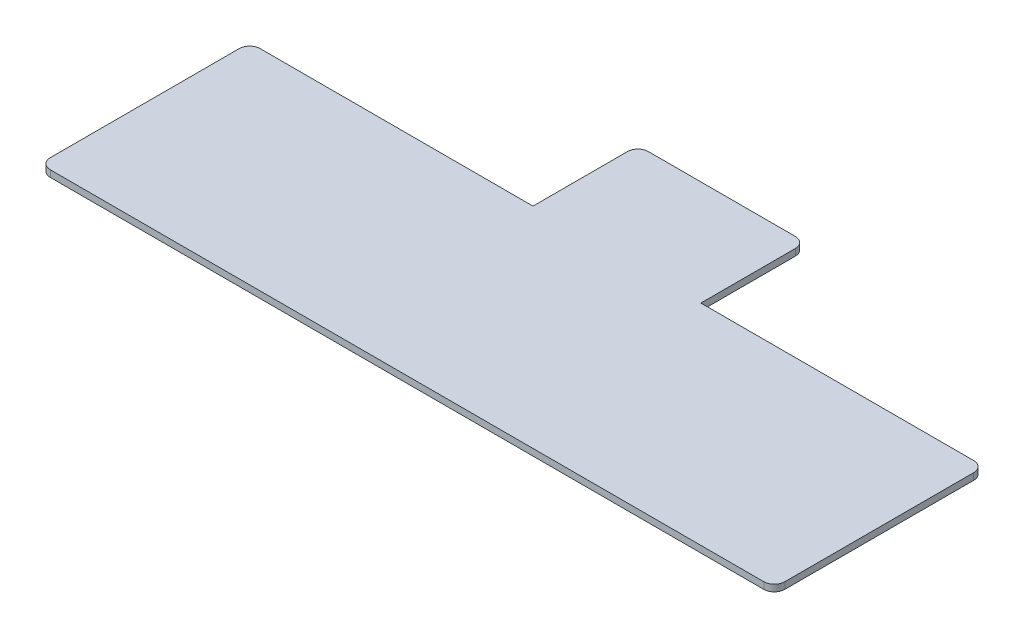
SolidWorks part; units mm, degrees
ref_plane "Front" through (0, 0, 0) normal (0, 0, 1) x (1, 0, 0)
ref_plane "Top" through (0, 0, 0) normal (0, 1, 0) x (1, 0, 0)
ref_plane "Right" through (0, 0, 0) normal (1, 0, 0) x (0, 0, -1)
sketch "Sketch1" plane through (0, 0, 0) normal (0, 1, 0) x (1, 0, 0)
  line L0 (215, 100) -> (350, 100)
  line L1 (0, 0) -> (350, 0)
  line L2 (0, 0) -> (0, 100)
  line L3 (0, 100) -> (135, 100)
  line L4 (350, 0) -> (350, 100)
  line L5 (175, 0) -> (175, 106.0721) construction
  line L6 (135, 100) -> (135, 150)
  line L7 (135, 150) -> (215, 150)
  line L8 (215, 100) -> (215, 150)
  dimension "D1" = 350
  dimension "D2" = 80
  dimension "D3" = 100
  dimension "D4" = 50
base flange "Base-Flange1" sketch "Sketch1" thickness 3.175 reverse thickness direction no parameters "D1"=1
fillet "Fillet1" radius 5 6 edges at (350, -1.5875, 0) (0, -1.5875, 0) (135, -1.5875, -150) (215, -1.5875, -150) (350, -1.5875, -100) (0, -1.5875, -100)
sketch "Bend-Lines1" [suppressed] plane through (0, 0, 0) normal (0, 1, 0) x (1, 0, 0)
sketch "Bounding-Box1" [suppressed] plane through (0, 0, 0) normal (0, 1, 0) x (1, 0, 0)
sheet metal parameters "Sheet-Metal1" thickness 3.175 parameters "D1"=1
flat pattern "Flat-Pattern1" [suppressed]
sketch "Bend-Lines2" plane through (0, 0, 0) normal (0, 1, 0) x (1, 0, 0)
sketch3d "Bounding-Box2" [suppressed]
  line L0 (0, 149.9999, 0) -> (350, 150.0001, 0) construction
  line L1 (0, 0, 0) -> (350, 0.0002, 0) construction
  line L2 (0, 149.9999, 0) -> (0, 0, 0) construction
  line L3 (350, 150.0001, 0) -> (350, 0.0002, 0) construction
